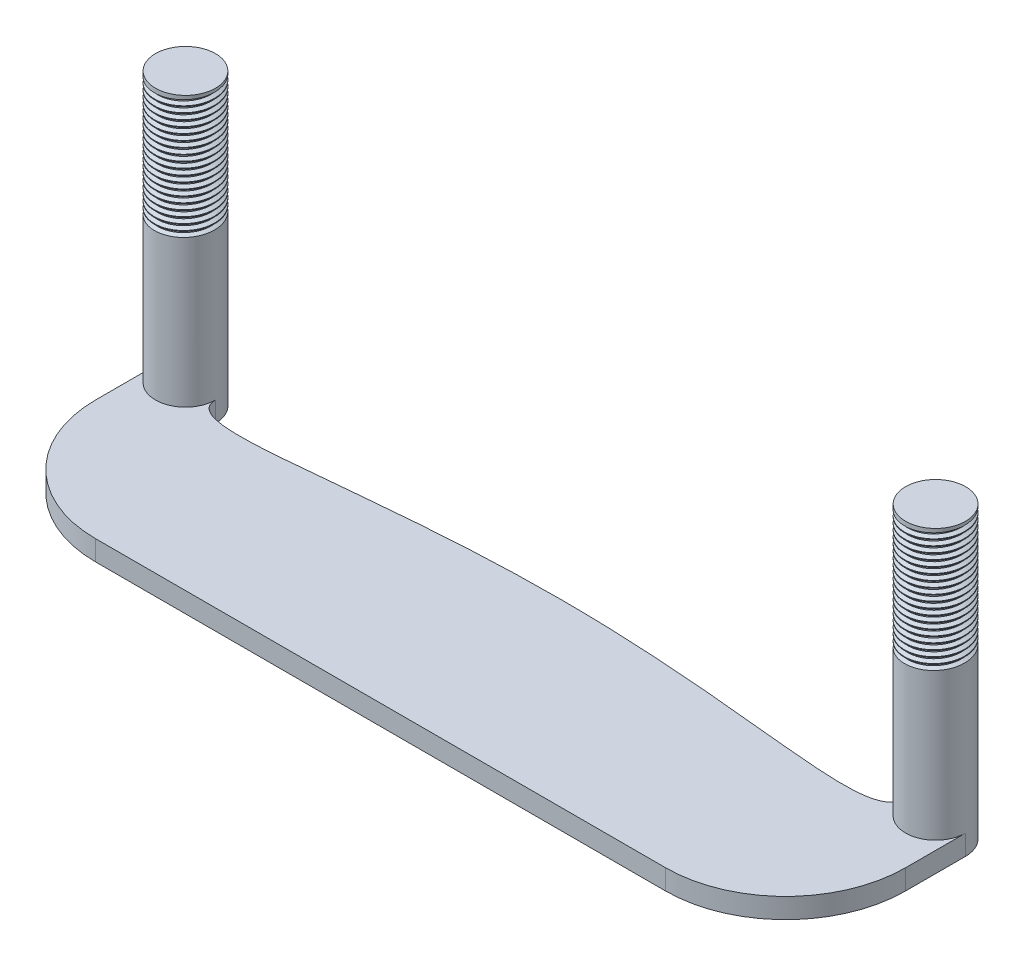
SolidWorks part; units mm, degrees
ref_plane "Front Plane" through (0, 0, 0) normal (0, 0, 1) x (1, 0, 0)
ref_plane "Top Plane" through (0, 0, 0) normal (0, 1, 0) x (1, 0, 0)
ref_plane "Right Plane" through (0, 0, 0) normal (1, 0, 0) x (0, 0, -1)
sketch "Sketch4" plane through (0, 0, 0) normal (0, 1, 0) x (1, 0, 0)
  line L0 (3.175, 9.525) -> (3.175, 7.239) construction
  line L1 (6.35, 0) -> (36.5125, 0)
  line L2 (0, 6.35) -> (0, 9.525)
  line L4 (42.8625, 6.35) -> (42.8625, 9.525)
  line L5 (3.175, 7.239) -> (10.541, 9.525) construction
  line L6 (10.541, 9.525) -> (21.4191, 9.525) construction
  line L8 (39.6875, 9.525) -> (39.6875, 7.239) construction
  line L9 (39.6875, 7.239) -> (32.3215, 9.525) construction
  line L10 (32.3215, 9.525) -> (21.4191, 9.525) construction
  arc A0 (3.175, 9.525) -> (0, 9.525) centre (1.5875, 9.525) ccw
  arc A1 (42.8625, 9.525) -> (39.6875, 9.525) centre (41.275, 9.525) ccw
  arc A2 (36.5125, 0) -> (42.8625, 6.35) centre (36.5125, 6.35) ccw
  arc A3 (0, 6.35) -> (6.35, 0) centre (6.35, 6.35) ccw
  spline S0 degree 3 poles (3.175, 9.525) (3.175, 7.239) (10.541, 9.525) (21.4191, 9.525) knots 0 0 0 0 1 1 1 1
  spline S1 degree 3 poles (39.6875, 9.525) (39.6875, 7.239) (32.3215, 9.525) (21.4191, 9.525) knots 0 0 0 0 1 1 1 1
  point P12 (21.4312, 0)
  point P13 (21.4312, 0)
  point P14 (0, 0)
  point P21 (0, 0)
  dimension "D5" = 9.525
  dimension "D6" = 9.525
  dimension "D3" = 1.5875
  dimension "D4" = 1.5875
  dimension "D10" = 18.7749
  dimension "D19" = 18.7991
  dimension "D20" = 6.35
  dimension "D1" = 42.8625
  dimension "D2" = 3.175
  dimension "D7" = 3.175
  dimension "D8" = 9.525
  dimension "D9" = 9.525
  dimension "D11" = 2.286
  dimension "D12" = 7.366
  dimension "D13" = 3.175
  dimension "D14" = 3.175
  dimension "D15" = 2.286
  dimension "D16" = 7.366
  dimension "D17" = 9.525
  dimension "D18" = 9.525
extrude "Boss-Extrude1" add sketch "Sketch4" along normal blind 1.0668
sketch "Sketch5" plane through (0, 1.0668, 0) normal (0, 1, 0) x (1, 0, 0)
  line L2 (6.35, 0) -> (36.5125, 0) construction
  line L3 (42.8625, 6.35) -> (42.8625, 9.525) construction
  line L4 (0, 9.525) -> (0, 6.35) construction
  circle A1 centre (41.275, 9.525) radius 1.5875
  circle A2 centre (1.5875, 9.525) radius 1.5875
  dimension "D2" = 3.175
  dimension "D1" = 9.525
  dimension "D6" = 3.175
  dimension "D3" = 1.5875
  dimension "D4" = 9.525
  dimension "D5" = 1.5875
extrude "Boss-Extrude2" add sketch "Sketch5" along normal blind 14.2875
thread "Thread1" pitch 0.3175 method cut profile "Thread Profile1" start angle 0, offset 0, length 6.35, pitch 0.3175, diameter 3.175
ref_plane "Plane1" through (0, 15.3543, -9.525) normal (0, 0, 1) x (-1, 0, 0)
sketch "Thread Profile1" plane through (0, 15.3543, -9.525) normal (0, 0, 1) x (-1, 0, 0)
  line L0 (0, 0) -> (0, 0.3175) construction
  line L11 (0, 0) -> (0, 0.2778)
  line L12 (0, 0.2778) -> (-0.1719, 0.1786)
  line L13 (-0.1719, 0.1786) -> (-0.1719, 0.0992)
  line L15 (-0.1719, 0.0992) -> (0, 0)
  line L17 (-0.1719, 0.1389) -> (0, 0.1389) construction
  point P2 (0, 0)
  dimension "Pitch" = 0.3175
  dimension "Profile_Angle" = 60
  dimension "Profile_Land" = 0.0794
  dimension "Profile_Height" = 0.1719
thread "Thread2" pitch 0.3175 method cut profile "Thread Profile2" start angle 0, offset 0, length 6.35, pitch 0.3175, diameter 3.175
ref_plane "Plane2" through (39.6875, 15.3543, -9.525) normal (0, 0, 1) x (-1, 0, 0)
sketch "Thread Profile2" plane through (39.6875, 15.3543, -9.525) normal (0, 0, 1) x (-1, 0, 0)
  line L0 (0, 0) -> (0, 0.3175) construction
  line L11 (0, 0) -> (0, 0.2778)
  line L12 (0, 0.2778) -> (-0.1719, 0.1786)
  line L13 (-0.1719, 0.1786) -> (-0.1719, 0.0992)
  line L15 (-0.1719, 0.0992) -> (0, 0)
  line L17 (-0.1719, 0.1389) -> (0, 0.1389) construction
  point P2 (0, 0)
  dimension "Pitch" = 0.3175
  dimension "Profile_Angle" = 60
  dimension "Profile_Land" = 0.0794
  dimension "Profile_Height" = 0.1719
